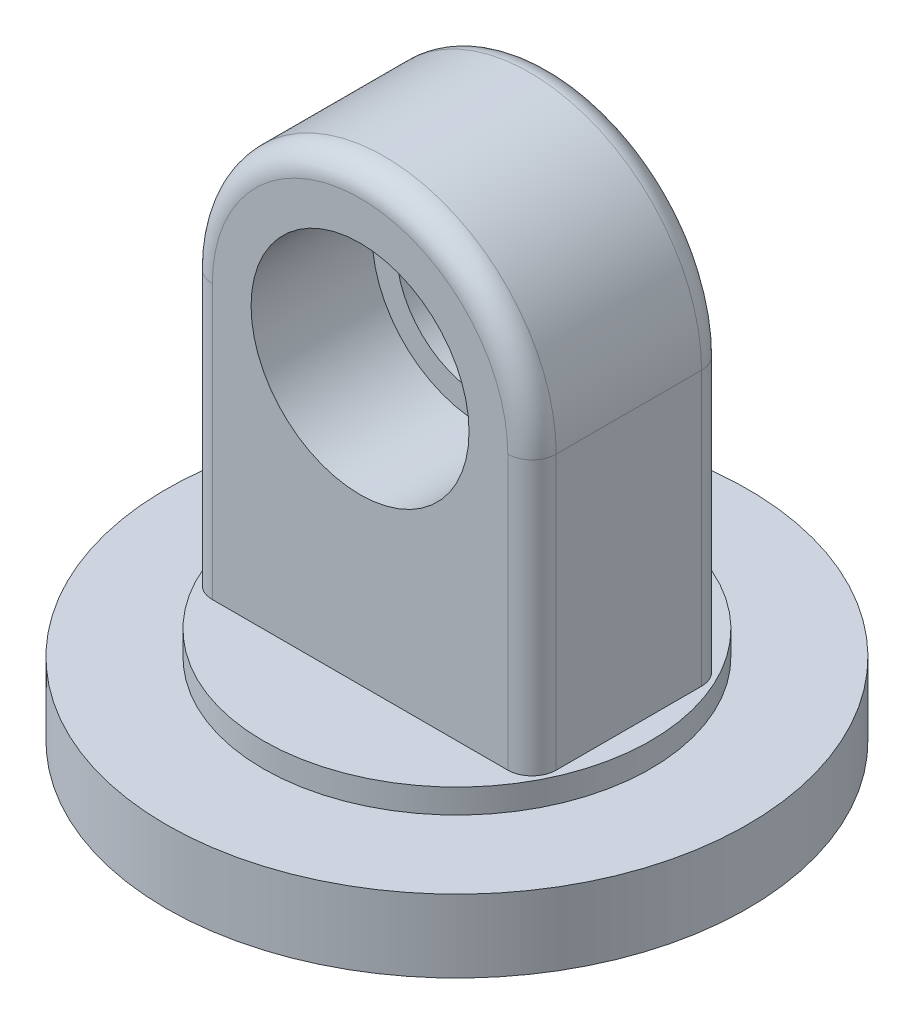
SolidWorks part; units mm, degrees
material "ﾎﾟﾘｴﾁﾚﾝｲﾐﾝ(PEI)"
ref_plane "正面" through (0, 0, 0) normal (0, 0, 1) x (1, 0, 0)
ref_plane "平面" through (0, 0, 0) normal (0, 1, 0) x (1, 0, 0)
ref_plane "右側面" through (0, 0, 0) normal (1, 0, 0) x (0, 0, -1)
sketch "ｽｹｯﾁ1" plane through (0, 0, 0) normal (0, 1, 0) x (1, 0, 0)
  circle A0 centre (0, 0) radius 6
  dimension "D1" = 12
extrude "ﾎﾞｽ - 押し出し1" add sketch "ｽｹｯﾁ1" along normal blind 1.5
sketch "ｽｹｯﾁ2" plane through (0, 1.5, 0) normal (0, 1, 0) x (1, 0, 0)
  circle A0 centre (0, 0) radius 4
  dimension "D1" = 8
extrude "ﾎﾞｽ - 押し出し2" add sketch "ｽｹｯﾁ2" along normal blind 0.5
sketch "ｽｹｯﾁ3" plane through (0, 0, 0) normal (0, -1, 0) x (1, 0, 0)
  circle A0 centre (0, 0) radius 4.5
  dimension "D1" = 9
extrude "ﾎﾞｽ - 押し出し3" add sketch "ｽｹｯﾁ3" along normal blind 0.5
sketch "ｽｹｯﾁ4" plane through (0, -0.5, 0) normal (0, -1, 0) x (1, 0, 0)
  circle A0 centre (0, 0) radius 3.5
  dimension "D1" = 7
extrude "ｶｯﾄ - 押し出し1" cut sketch "ｽｹｯﾁ4" against normal blind 0.5
sketch "ｽｹｯﾁ8" plane through (0, 0, 0) normal (0, 0, 1) x (1, 0, 0)
  line L0 (0, -0.5) -> (0, 11.2) construction
  line L1 (-4.5, -0.5) -> (4.5, -0.5) construction
  line L2 (-3.55, 2) -> (-3.55, 7.65)
  line L3 (4, 2) -> (-4, 2) construction
  line L4 (3.55, 7.65) -> (3.55, 2)
  line L5 (-3.55, 2) -> (3.55, 2)
  arc A0 (-3.55, 7.65) -> (3.55, 7.65) centre (0, 7.65) cw
  circle A1 centre (0, 7.65) radius 1.75
  dimension "D3" = 3.5
  dimension "D1" = 9.2
  dimension "D2" = 7.1
extrude "ﾎﾞｽ - 押し出し5" add sketch "ｽｹｯﾁ8" along normal mid plane 4
sketch "ｽｹｯﾁ9" plane through (0, 0, 2) normal (0, 0, 1) x (1, 0, 0)
  circle A0 centre (0, 7.65) radius 2.25
  dimension "D1" = 4.5
extrude "ｶｯﾄ - 押し出し3" cut sketch "ｽｹｯﾁ9" against normal blind 2.5
fillet "ﾌｨﾚｯﾄ1" radius 0.5 6 edges at (-3.55, 4.825, -2) (0, 11.2, -2) (-3.55, 4.825, 2) (0, 11.2, 2) (3.55, 4.825, -2) (3.55, 4.825, 2)
sketch "ｽｹｯﾁ5" plane through (0, 0, 0) normal (0, -1, 0) x (1, 0, 0)
  circle A0 centre (0, 0) radius 1.2
  dimension "D1" = 2.4
extrude "ｶｯﾄ - 押し出し2" cut sketch "ｽｹｯﾁ5" against normal blind 2.4
